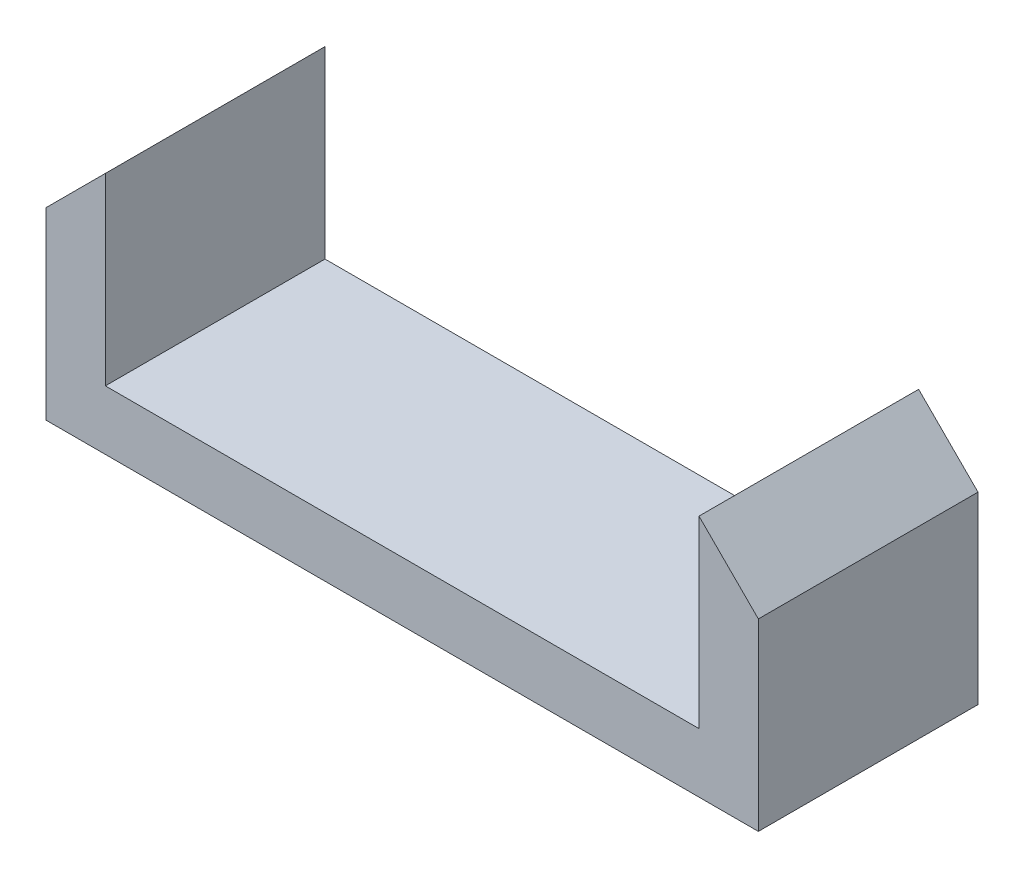
SolidWorks part; units mm, degrees
ref_plane "Front Plane" through (0, 0, 0) normal (0, 0, 1) x (1, 0, 0)
ref_plane "Top Plane" through (0, 0, 0) normal (0, 1, 0) x (1, 0, 0)
ref_plane "Right Plane" through (0, 0, 0) normal (1, 0, 0) x (0, 0, -1)
sketch "Sketch1" plane through (0, 0, 0) normal (0, 0, 1) x (1, 0, 0)
  line L1 (-12, 13.2101) -> (0, 13.2101)
  line L2 (-12, 13.2101) -> (-12, 9.1101)
  line L3 (-12, 9.1101) -> (0, 9.1101)
  line L4 (0, 13.2101) -> (0, 9.1101)
  dimension "D1" = 12
  dimension "D2" = 4.1
extrude "Boss-Extrude1" add sketch "Sketch1" along normal blind 3.7
sketch "Sketch3" plane through (0, 0, 3.7) normal (0, 0, 1) x (1, 0, 0)
  line L0 (-1, 13.2101) -> (0, 13.2101)
  line L1 (0, 13.2101) -> (-12, 13.2101) construction
  line L2 (0, 13.2101) -> (0, 12.2101)
  line L3 (0, 9.1101) -> (0, 13.2101) construction
  line L4 (0, 12.2101) -> (-1, 13.2101)
  dimension "D1" = 1
  dimension "D2" = 1
extrude "Cut-Extrude1" cut sketch "Sketch3" against normal blind 3.7
sketch "Sketch4" plane through (0, 0, 3.7) normal (0, 0, 1) x (1, 0, 0)
  line L0 (-12, 13.2101) -> (-11, 13.2101)
  line L1 (-1, 13.2101) -> (-12, 13.2101) construction
  line L2 (-11, 13.2101) -> (-12, 12.2101)
  line L3 (-12, 13.2101) -> (-12, 9.1101) construction
  line L4 (-12, 12.2101) -> (-12, 13.2101)
  dimension "D1" = 1
  dimension "D2" = 1
extrude "Cut-Extrude2" cut sketch "Sketch4" against normal blind 3.7
sketch "Sketch5" plane through (0, 9.1101, 0) normal (0, -1, 0) x (1, 0, 0)
  line L0 (-12, 3.7) -> (0, 3.7) construction
  line L1 (-12, 3.7) -> (-12, 0) construction
  circle A0 centre (-6, 1.7) radius 1.3
  dimension "D3" = 2.6
  dimension "D1" = 2
  dimension "D2" = 6
extrude "Boss-Extrude2" add sketch "Sketch5" along normal blind 0.4
fillet "Fillet1" radius 0.5 1 edges at (-6, 8.7101, 0.4)
sketch "Sketch6" plane through (0, 0, 3.7) normal (0, 0, 1) x (1, 0, 0)
  line L0 (-12, 9.1101) -> (0, 9.1101) construction
  line L1 (-11, 13.2101) -> (-1, 13.2101)
  line L2 (-11, 13.2101) -> (-11, 10.1101)
  line L3 (-11, 10.1101) -> (-1, 10.1101)
  line L4 (-1, 13.2101) -> (-1, 10.1101)
  dimension "D1" = 1
extrude "Cut-Extrude3" cut sketch "Sketch6" against normal through all
